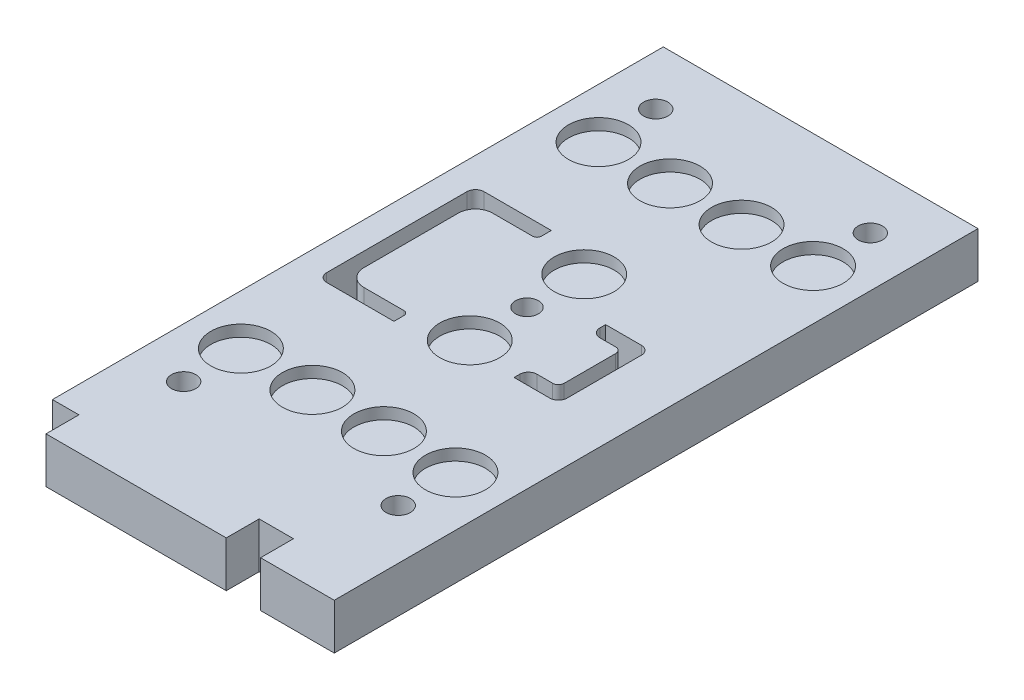
SolidWorks part; units mm, degrees
material "Plain Carbon Steel"
ref_plane "Front Plane" through (0, 0, 0) normal (0, 0, 1) x (1, 0, 0)
ref_plane "Top Plane" through (0, 0, 0) normal (0, 1, 0) x (1, 0, 0)
ref_plane "Right Plane" through (0, 0, 0) normal (1, 0, 0) x (0, 0, -1)
sketch "Sketch1" plane through (0, 0, 0) normal (0, 1, 0) x (1, 0, 0)
  line L1 (-55, -112.5) -> (55, -112.5)
  line L2 (-55, -112.5) -> (-55, 112.5)
  line L3 (-55, 112.5) -> (55, 112.5)
  line L4 (55, -112.5) -> (55, 112.5)
  line L5 (-55, -112.5) -> (55, 112.5) construction
  line L6 (-55, 112.5) -> (55, -112.5) construction
  point P0 (0, 0)
  dimension "D1" = 110
  dimension "D2" = 225
extrude "Boss-Extrude1" add sketch "Sketch1" against normal blind 16
sketch "Sketch2" plane through (0, 0, 0) normal (0, 1, 0) x (1, 0, 0)
  line L0 (-19, 37.36) -> (-19, 33.86) construction
  line L1 (-42.5, 37.36) -> (-19, 37.36) construction
  line L2 (-45.5, 34.36) -> (-45.5, -14.64) construction
  line L3 (-42.5, -17.64) -> (-19, -17.64) construction
  line L4 (-19, -17.64) -> (-19, -14.14) construction
  line L5 (-34.5, -12.64) -> (-20.5, -12.64) construction
  line L6 (-40.5, 26.36) -> (-40.5, -6.64) construction
  line L7 (-20.5, 32.36) -> (-34.5, 32.36) construction
  line L8 (-19, 37.36) -> (-19, 33.86)
  line L9 (-42.5, 37.36) -> (-19, 37.36)
  line L10 (-45.5, 34.36) -> (-45.5, -14.64)
  line L11 (-42.5, -17.64) -> (-19, -17.64)
  line L12 (-19, -17.64) -> (-19, -14.14)
  line L13 (-34.5, -12.64) -> (-20.5, -12.64)
  line L14 (-40.5, 26.36) -> (-40.5, -6.64)
  line L15 (-20.5, 32.36) -> (-34.5, 32.36)
  arc A0 (-20.5, 32.36) -> (-19, 33.86) centre (-20.5, 33.86) ccw construction
  arc A1 (-42.5, 37.36) -> (-45.5, 34.36) centre (-42.5, 34.36) ccw construction
  arc A2 (-45.5, -14.64) -> (-42.5, -17.64) centre (-42.5, -14.64) ccw construction
  arc A3 (-19, -14.14) -> (-20.5, -12.64) centre (-20.5, -14.14) ccw construction
  arc A4 (-40.5, -6.64) -> (-34.5, -12.64) centre (-34.5, -6.64) ccw construction
  arc A5 (-34.5, 32.36) -> (-40.5, 26.36) centre (-34.5, 26.36) ccw construction
  arc A6 (-20.5, 32.36) -> (-19, 33.86) centre (-20.5, 33.86) ccw
  arc A7 (-42.5, 37.36) -> (-45.5, 34.36) centre (-42.5, 34.36) ccw
  arc A8 (-45.5, -14.64) -> (-42.5, -17.64) centre (-42.5, -14.64) ccw
  arc A9 (-19, -14.14) -> (-20.5, -12.64) centre (-20.5, -14.14) ccw
  arc A10 (-40.5, -6.64) -> (-34.5, -12.64) centre (-34.5, -6.64) ccw
  arc A11 (-34.5, 32.36) -> (-40.5, 26.36) centre (-34.5, 26.36) ccw
extrude "Cut-Extrude1" cut sketch "Sketch2" against normal up to next
sketch "Sketch3" plane through (0, 0, 0) normal (0, 1, 0) x (1, 0, 0)
  line L0 (19, 18.36) -> (31.5, 18.36) construction
  line L1 (19, 18.36) -> (19, 16.36) construction
  line L2 (27.5, 13.36) -> (22, 13.36) construction
  line L3 (29.5, -6.64) -> (29.5, 11.36) construction
  line L4 (22, -8.64) -> (27.5, -8.64) construction
  line L5 (19, -13.64) -> (19, -11.64) construction
  line L6 (31.5, -13.64) -> (19, -13.64) construction
  line L7 (34.5, 15.36) -> (34.5, -10.64) construction
  line L8 (19, 18.36) -> (31.5, 18.36)
  line L9 (19, 18.36) -> (19, 16.36)
  line L10 (27.5, 13.36) -> (22, 13.36)
  line L11 (29.5, -6.64) -> (29.5, 11.36)
  line L12 (22, -8.64) -> (27.5, -8.64)
  line L13 (19, -13.64) -> (19, -11.64)
  line L14 (31.5, -13.64) -> (19, -13.64)
  line L15 (34.5, 15.36) -> (34.5, -10.64)
  arc A0 (34.5, 15.36) -> (31.5, 18.36) centre (31.5, 15.36) ccw construction
  arc A1 (19, 16.36) -> (22, 13.36) centre (22, 16.36) ccw construction
  arc A2 (29.5, 11.36) -> (27.5, 13.36) centre (27.5, 11.36) ccw construction
  arc A3 (27.5, -8.64) -> (29.5, -6.64) centre (27.5, -6.64) ccw construction
  arc A4 (22, -8.64) -> (19, -11.64) centre (22, -11.64) ccw construction
  arc A5 (31.5, -13.64) -> (34.5, -10.64) centre (31.5, -10.64) ccw construction
  arc A6 (34.5, 15.36) -> (31.5, 18.36) centre (31.5, 15.36) ccw
  arc A7 (19, 16.36) -> (22, 13.36) centre (22, 16.36) ccw
  arc A8 (29.5, 11.36) -> (27.5, 13.36) centre (27.5, 11.36) ccw
  arc A9 (27.5, -8.64) -> (29.5, -6.64) centre (27.5, -6.64) ccw
  arc A10 (22, -8.64) -> (19, -11.64) centre (22, -11.64) ccw
  arc A11 (31.5, -13.64) -> (34.5, -10.64) centre (31.5, -10.64) ccw
extrude "Cut-Extrude2" cut sketch "Sketch3" against normal up to next
sketch "Sketch4" plane through (0, -16, 0) normal (0, -1, 0) x (1, 0, 0)
  circle A0 centre (0, 100) radius 8.5
  circle A1 centre (0, -100) radius 8.5
  dimension "D1" = 17
extrude "Cut-Extrude3" cut sketch "Sketch4" against normal blind 5
sketch "Sketch5" plane through (0, 0, 0) normal (0, 1, 0) x (1, 0, 0)
  line L2 (-55, 112.5) -> (-55, -112.5) construction
  line L5 (-19, 37.36) -> (-42.5, 37.36) construction
  line L6 (-40.5, 9.86) -> (29.5, 9.86) construction
  line L7 (-40.5, -6.64) -> (-40.5, 26.36) construction
  line L9 (29.5, 11.36) -> (29.5, -6.64) construction
  circle A0 centre (-37.5, 72.36) radius 10.5
  circle A1 centre (-12.5, 72.36) radius 10.5
  circle A2 centre (12.5, 72.36) radius 10.5
  circle A3 centre (37.5, 72.36) radius 10.5
  circle A4 centre (37.5, -52.64) radius 10.5
  circle A5 centre (12.5, -52.64) radius 10.5
  circle A6 centre (-12.5, -52.64) radius 10.5
  circle A7 centre (-37.5, -52.64) radius 10.5
  circle A8 centre (0, 29.86) radius 10.5
  circle A9 centre (0, -10.14) radius 10.5
  dimension "D1" = 21
  dimension "D2" = 17.5
  dimension "D3" = 35
  dimension "D5" = 25
  dimension "D6" = 20
  dimension "D7" = 20
  dimension "D4" = 4
extrude "Cut-Extrude4" cut sketch "Sketch5" against normal blind 4
sketch "Sketch6" plane through (0, 0, 0) normal (0, 1, 0) x (1, 0, 0)
  line L0 (-55, -112.5) -> (55, -112.5) construction
  line L1 (29.25, -112.5) -> (17.25, -112.5)
  line L2 (29.25, -112.5) -> (29.25, -101)
  line L3 (29.25, -101) -> (17.25, -101)
  line L4 (17.25, -112.5) -> (17.25, -101)
  line L5 (18.75, -102) -> (27.75, -102) construction
  line L6 (-45.75, -112.5) -> (-57.75, -112.5)
  line L7 (-45.75, -112.5) -> (-45.75, -101)
  line L8 (-45.75, -101) -> (-57.75, -101)
  line L9 (-57.75, -112.5) -> (-57.75, -101)
  line L10 (28.25, -102.5) -> (28.25, -115) construction
  line L11 (18.25, -115) -> (18.25, -102.5) construction
  line L12 (-56.75, -115) -> (-56.75, -102.5) construction
  line L13 (-46.75, -102.5) -> (-46.75, -115) construction
  line L14 (-56.25, -102) -> (-47.25, -102) construction
  dimension "D1" = 1
  dimension "D2" = 1
  dimension "D3" = 1
  dimension "D4" = 1
  dimension "D5" = 1
  dimension "D6" = 1
extrude "Cut-Extrude5" cut sketch "Sketch6" against normal up to next
hole_wizard "M10 Tapped Hole1" positions "Sketch9" profile "Sketch8" tap size "M10" standard "ISO" end condition through all
sketch "Sketch9" plane through (0, 0, 0) normal (0, 1, 0) x (1, 0, 0)
  line L2 (-37.5, 72.36) -> (-37.5, 92.36) construction
  line L4 (37.5, 72.36) -> (37.5, 92.36) construction
  circle A1 centre (-37.5, 72.36) radius 10.5 construction
  circle A2 centre (-37.5, -52.64) radius 10.5 construction
  point P0 (-37.5, -72.64)
  point P2 (37.5, -72.64)
  point P4 (37.5, 92.36)
  point P6 (-37.5, 92.36)
  dimension "D1" = 20
  dimension "D2" = 20
sketch "Sketch8" plane through (-37.5, 0, 72.64) normal (1, 0, 0) x (0, 0, 1)
  line L0 (0, 0) -> (0, 16)
  line L1 (0, 16) -> (4.25, 16)
  line L2 (4.25, 16) -> (4.25, 0)
  line L5 (4.25, 0) -> (0, 0)
  line L11 (0, -6.35) -> (0, 107.95) construction
  dimension "Thru Tap Drill Dia." = 8.5
  dimension "Thru Tap Drill Depth" = 16
cosmetic thread "Hole Thread1" parameters "D2"=10
cosmetic thread "Hole Thread2" parameters "D2"=10
cosmetic thread "Hole Thread3" parameters "D2"=10
cosmetic thread "Hole Thread4" parameters "D2"=10
sketch "Sketch10" plane through (0, 0, 0) normal (0, 1, 0) x (1, 0, 0)
  circle A0 centre (0, 9.86) radius 5 construction
  circle A1 centre (0, 9.86) radius 5 construction
  circle A2 centre (0, 9.86) radius 4
  dimension "D1" = 8
extrude "Cut-Extrude6" cut sketch "Sketch10" against normal up to next
